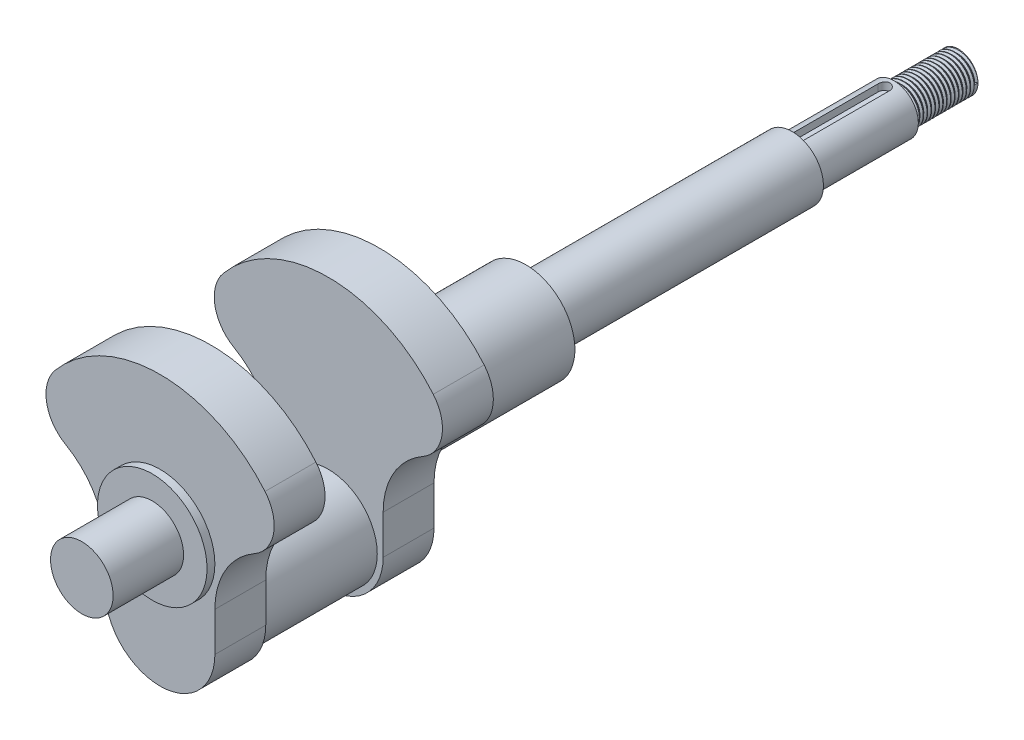
SolidWorks part; units mm, degrees
ref_plane "前视基准面" through (0, 0, 0) normal (0, 0, 1) x (1, 0, 0)
ref_plane "上视基准面" through (0, 0, 0) normal (0, 1, 0) x (1, 0, 0)
ref_plane "右视基准面" through (0, 0, 0) normal (1, 0, 0) x (0, 0, -1)
sketch "草图1" plane through (0, 0, 0) normal (0, 0, 1) x (1, 0, 0)
  line L0 (14, -20) -> (14, -10)
  line L1 (0, -41.3436) -> (0, 40.7098) construction
  line L2 (-14, -20) -> (-14, -10)
  arc A0 (26.8134, 22.4954) -> (-26.8134, 22.4954) centre (0, 0) ccw
  arc A1 (-14, -20) -> (14, -20) centre (0, -20) ccw
  arc A2 (24.1016, 7.3788) -> (14, -10) centre (34, -10) ccw
  arc A3 (24.1016, 7.3788) -> (26.8134, 22.4954) centre (19.1524, 16.0682) ccw
  arc A4 (-24.1016, 7.3788) -> (-14, -10) centre (-34, -10) cw
  arc A5 (-24.1016, 7.3788) -> (-26.8134, 22.4954) centre (-19.1524, 16.0682) cw
  dimension "D1" = 70
  dimension "D2" = 28
  dimension "D5" = 40
  dimension "D6" = 20
  dimension "D3" = 20
  dimension "D4" = 10
extrude "凸台-拉伸1" add sketch "草图1" along normal mid plane 56
extrude "切除-拉伸1" cut sketch "草图1<2>" against normal mid plane 30
sketch "草图1<2>" plane through (0, 0, 0) normal (0, 0, 1) x (1, 0, 0) same geometry as "草图1"
sketch "草图2" plane through (0, 0, -15) normal (0, 0, 1) x (1, 0, 0)
  circle A0 centre (0, -20) radius 12.5
  dimension "D1" = 25
extrude "凸台-拉伸2" add sketch "草图2" along normal blind 30
sketch "草图3" plane through (0, 0, 28) normal (0, 0, 1) x (1, 0, 0)
  circle A0 centre (0, 0) radius 14
  dimension "D1" = 28
extrude "凸台-拉伸3" add sketch "草图3" along normal blind 2
sketch "草图4" plane through (0, 0, 30) normal (0, 0, 1) x (1, 0, 0)
  circle A0 centre (0, 0) radius 8
  dimension "D1" = 16
extrude "凸台-拉伸4" add sketch "草图4" along normal blind 18
sketch "草图5" plane through (0, 0, -28) normal (0, 0, -1) x (-1, 0, 0)
  circle A0 centre (0, 0) radius 14
  dimension "D1" = 28
extrude "凸台-拉伸5" add sketch "草图5" along normal blind 2
sketch "草图6" plane through (0, 0, -30) normal (0, 0, -1) x (-1, 0, 0)
  circle A0 centre (0, 0) radius 12.5
  dimension "D1" = 25
extrude "凸台-拉伸6" add sketch "草图6" along normal blind 35.5
sketch "草图7" plane through (0, 0, -65.5) normal (0, 0, -1) x (-1, 0, 0)
  circle A0 centre (0, 0) radius 8
  dimension "D1" = 16
extrude "凸台-拉伸7" add sketch "草图7" along normal blind 68
sketch "草图8" plane through (0, 0, -133.5) normal (0, 0, -1) x (-1, 0, 0)
  circle A0 centre (0, 0) radius 6.25
  dimension "D1" = 12.5
extrude "凸台-拉伸8" add sketch "草图8" along normal blind 26
sketch "草图9" plane through (0, 0, -159.5) normal (0, 0, -1) x (-1, 0, 0)
  circle A0 centre (0, 0) radius 5
  dimension "D1" = 10
extrude "凸台-拉伸9" add sketch "草图9" along normal blind 16.5
ref_plane "基准面1" through (0, 4.25, 0) normal (0, 1, 0) x (1, 0, 0)
sketch "草图11" plane through (0, 4.25, 0) normal (0, 1, 0) x (1, 0, 0)
  line L0 (0, 135) -> (0, 157) construction
  line L1 (-1.5, 135) -> (-1.5, 157)
  line L2 (1.5, 135) -> (1.5, 157)
  line L3 (8, 133.5) -> (-8, 133.5) construction
  arc A0 (-1.5, 135) -> (1.5, 135) centre (0, 135) ccw
  arc A1 (1.5, 157) -> (-1.5, 157) centre (0, 157) ccw
  point P3 (0, 146)
  dimension "D1" = 1.5
  dimension "D2" = 22
  dimension "D3" = 1.5
extrude "切除-拉伸2" cut sketch "草图11" along normal blind 16.5
thread "螺纹线1" pitch 1 method cut profile "螺纹线轮廓1" start angle 0, offset 0, length 16.5, pitch 1, diameter 10
ref_plane "基准面2" through (5, 0, -176) normal (0, -1, 0) x (1, 0, 0)
sketch "螺纹线轮廓1" plane through (5, 0, -176) normal (0, -1, 0) x (1, 0, 0)
  line L0 (0, 0) -> (0, 1) construction
  line L11 (0, 0) -> (0, 0.875)
  line L12 (0, 0.875) -> (-0.5413, 0.5625)
  line L13 (-0.5413, 0.5625) -> (-0.5413, 0.3125)
  line L15 (-0.5413, 0.3125) -> (0, 0)
  line L17 (-0.5413, 0.4375) -> (0, 0.4375) construction
  point P2 (0, 0)
  dimension "Pitch" = 1
  dimension "Profile_Angle" = 60
  dimension "Profile_Land" = 0.25
  dimension "Profile_Height" = 0.5413
